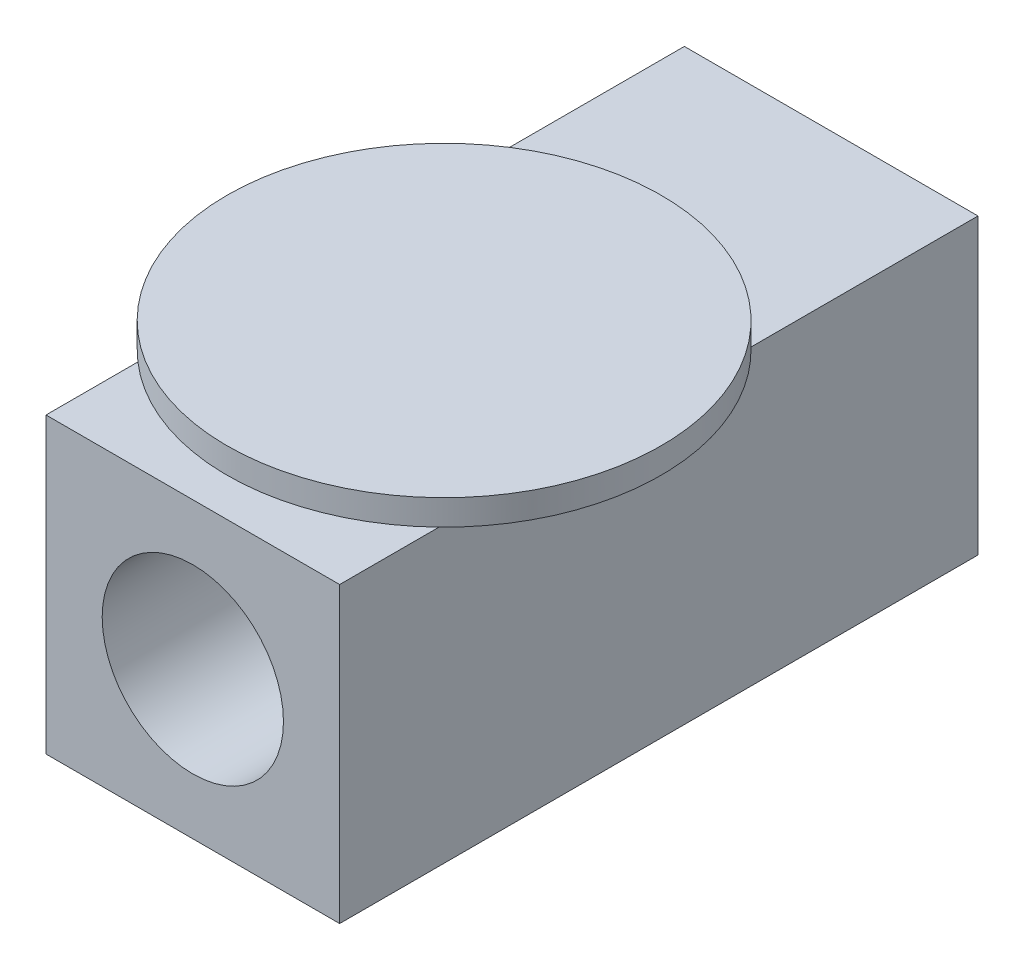
SolidWorks part; units mm, degrees
material "ABS generico"
ref_plane "Piano frontale" through (0, 0, 0) normal (0, 0, 1) x (1, 0, 0)
ref_plane "Piano superiore" through (0, 0, 0) normal (0, 1, 0) x (1, 0, 0)
ref_plane "Piano destro" through (0, 0, 0) normal (1, 0, 0) x (0, 0, -1)
sketch "Schizzo1" plane through (0, 0, 0) normal (0, 0, 1) x (1, 0, 0)
  line L4 (-7.3767, -9.877) -> (-7.3597, -9.8281)
  line L24 (7.9489, 13.813) -> (-15.0511, 13.813)
  line L25 (7.9489, 13.813) -> (7.9489, -9.187)
  line L26 (7.9489, -9.187) -> (-15.0511, -9.187)
  line L27 (-15.0511, 13.813) -> (-15.0511, -9.187)
  dimension "D1" = 23
extrude "Estrusione-Estrusione1" add sketch "Schizzo1" along normal blind 50 contours L24 L27 L26 L25 region at (-3.5511, 2.313, 0)
sketch "Schizzo3" plane through (0, 13.813, 0) normal (0, 1, 0) x (1, 0, 0)
  line L0 (7.9489, -50) -> (-15.0511, -50) construction
  circle A0 centre (-3.869, -30) radius 17
  dimension "D1" = 34
  dimension "D2" = 20
sketch "Schizzo18" plane through (0, 0, 0) normal (0, 0, -1) x (-1, 0, 0)
  line L0 (-7.9489, 2.313) -> (15.0511, 2.313) construction
  line L1 (-7.9489, 13.813) -> (-7.9489, -9.187) construction
  line L2 (15.0511, 13.813) -> (15.0511, -9.187) construction
  line L3 (3.5511, 13.813) -> (3.5511, -9.187) construction
  line L4 (-7.9489, 13.813) -> (15.0511, 13.813) construction
  line L5 (-7.9489, -9.187) -> (15.0511, -9.187) construction
  circle A0 centre (3.5511, 2.313) radius 7.1
  dimension "D1" = 14.2
extrude "Taglio-Estrusione12" cut sketch "Schizzo18" against normal up to next
chamfer "Smusso4" distance 1 distance2 3 1 edges at (-10.6511, 2.313, 0) first distance on face at (-10.6511, 2.313, 0)
extrude "Estrusione-Estrusione2" add sketch "Schizzo3" along normal blind 2
